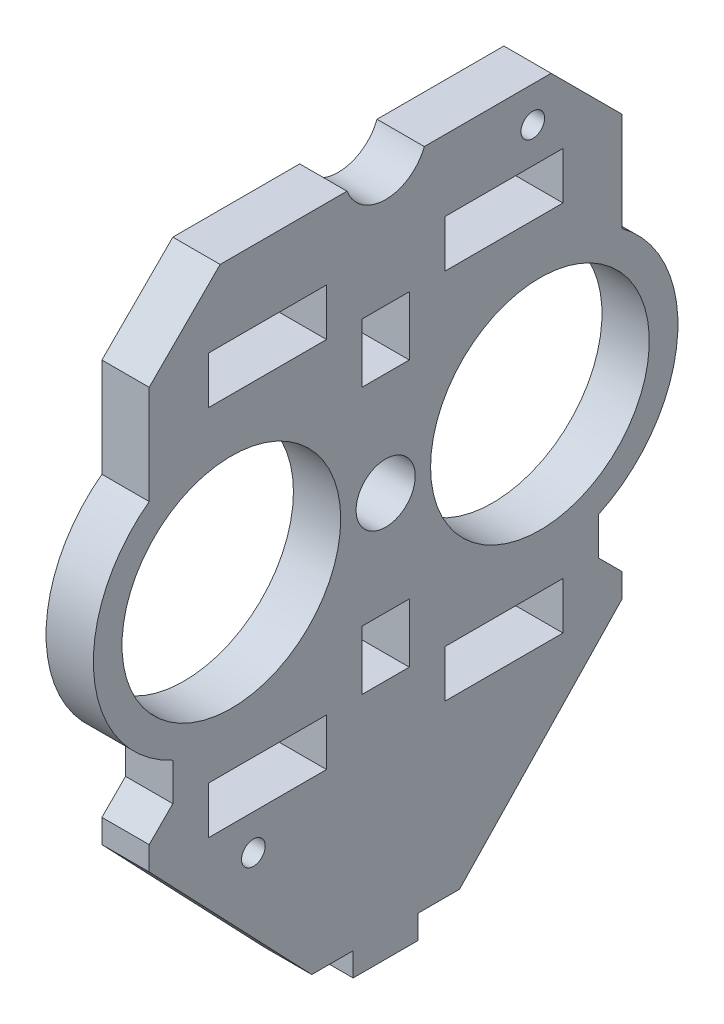
SolidWorks part; units mm, degrees
ref_plane "Front Plane" through (0, 0, 0) normal (0, 0, 1) x (1, 0, 0)
ref_plane "Top Plane" through (0, 0, 0) normal (0, 1, 0) x (1, 0, 0)
ref_plane "Right Plane" through (0, 0, 0) normal (1, 0, 0) x (0, 0, -1)
sketch "Sketch1" plane through (0, 0, 0) normal (1, 0, 0) x (0, 0, -1)
  line L0 (0, 86.3618) -> (0, -95.6447) construction
  line L1 (-34.45, 0) -> (67.35, 0) construction
  line L2 (-12.5, -64.29) -> (-40, -35.5)
  line L3 (-40, -31.5) -> (-40, -35.5)
  line L4 (-40, -31.5) -> (-36, -27.5)
  line L5 (-12.5, -64.29) -> (-12.5, -68.29)
  line L6 (-12.5, -68.29) -> (12.5, -68.29)
  line L7 (12.5, -64.29) -> (12.5, -68.29)
  line L8 (-36, -27.5) -> (-36, -21.1431)
  line L9 (-40, 35.5) -> (-40, 18.7571)
  line L10 (-40, 35.5) -> (-28, 47.5)
  line L11 (40, 35.5) -> (-40, 35.5) construction
  line L12 (40, 35.5) -> (40, 18.7571)
  line L13 (40, -35.5) -> (40, -31.5)
  line L14 (40, -31.5) -> (36, -27.5)
  line L15 (36, -27.5) -> (36, -21.1431)
  line L16 (12.5, -64.29) -> (40, -35.5)
  line L17 (40, -35.5) -> (30, -35.5) construction
  line L18 (40, 35.5) -> (28, 47.5)
  line L19 (-28, 47.5) -> (28, 47.5) construction
  line L20 (-28, 47.5) -> (-6.5383, 47.5)
  line L21 (6.5383, 47.5) -> (28, 47.5)
  line L22 (-40, -35.5) -> (-40, -27.5) construction
  line L24 (-30, -27.5) -> (-40, -27.5) construction
  circle A0 centre (0, 0) radius 76.29 construction
  circle A1 centre (-22.3739, -41.5) radius 2
  circle A2 centre (24.8916, 41.5) radius 2
  circle A3 centre (-26.1, 0) radius 23.3461 construction
  circle A4 centre (-26.1, 0) radius 18.5
  circle A5 centre (26.1, 0) radius 18.5
  circle A6 centre (26.1, 0) radius 23.3461 construction
  circle A7 centre (0, 0) radius 5
  circle A8 centre (0, 50) radius 7 construction
  arc A9 (-40, 18.7571) -> (-36, -21.1431) centre (-26.1, 0) ccw
  arc A10 (40, 18.7571) -> (36, -21.1431) centre (26.1, 0) cw
  circle A11 centre (-26.1, 0) radius 8.35 construction
  arc A12 (-6.5383, 47.5) -> (6.5383, 47.5) centre (0, 50) ccw
  circle A13 centre (70, 0) radius 2.65 construction
  circle A14 centre (-43.3013, -25) radius 7 construction
  point P14 (0, 0)
  point P16 (0, -76.29)
  point P20 (-62.4774, 0)
  point P27 (0, -68.29)
  point P30 (0, 56.7762)
  point P31 (0, 56.7762)
  dimension "D1" = 152.58
  dimension "D2" = 4
  dimension "D5" = 37
  dimension "D9" = 8
  dimension "D7" = 6
  dimension "D10" = 4
  dimension "D3" = 6
  dimension "D4" = 4
  dimension "D13" = 10
  dimension "D6" = 124.9548
  dimension "D8" = 25
  dimension "D11" = 12
  dimension "D12" = 12
  dimension "D15" = 4
extrude "Boss-Extrude1" add sketch "Sketch1" along normal blind 8
sketch "Sketch2" plane through (0, 0, 0) normal (-1, 0, 0) x (0, 0, 1)
  line L0 (0, -90.2636) -> (0, 91.611) construction
  line L1 (-93.4475, 0) -> (84.8595, 0) construction
  line L2 (10, -27.5) -> (10, -35.5)
  line L3 (-30, -27.5) -> (-10, -27.5)
  line L4 (-30, -27.5) -> (-30, -35.5)
  line L5 (-30, -35.5) -> (-10, -35.5)
  line L6 (-10, -27.5) -> (-10, -35.5)
  line L7 (30, -35.5) -> (10, -35.5)
  line L8 (30, -27.5) -> (30, -35.5)
  line L9 (30, -27.5) -> (10, -27.5)
  line L10 (30, 27.5) -> (10, 27.5)
  line L11 (30, 27.5) -> (30, 35.5)
  line L12 (30, 35.5) -> (10, 35.5)
  line L13 (-10, 27.5) -> (-10, 35.5)
  line L14 (-30, 35.5) -> (-10, 35.5)
  line L15 (-30, 27.5) -> (-30, 35.5)
  line L16 (-30, 27.5) -> (-10, 27.5)
  line L17 (10, 27.5) -> (10, 35.5)
  line L18 (4, 17.5) -> (4, 27.5)
  line L19 (-4, -17.5) -> (4, -17.5)
  line L20 (-4, -17.5) -> (-4, -27.5)
  line L21 (-4, -27.5) -> (4, -27.5)
  line L22 (4, -17.5) -> (4, -27.5)
  line L23 (-4, 27.5) -> (4, 27.5)
  line L24 (-4, 17.5) -> (-4, 27.5)
  line L25 (-4, 17.5) -> (4, 17.5)
  line L26 (5.5, -68.29) -> (5.5, -64.29)
  line L27 (-12.5, -68.29) -> (-5.5, -68.29)
  line L28 (-12.5, -68.29) -> (-12.5, -64.29)
  line L29 (-12.5, -64.29) -> (-5.5, -64.29)
  line L30 (-5.5, -68.29) -> (-5.5, -64.29)
  line L31 (12.5, -64.29) -> (5.5, -64.29)
  line L32 (12.5, -68.29) -> (12.5, -64.29)
  line L33 (12.5, -68.29) -> (5.5, -68.29)
  point P26 (0, -17.5)
  dimension "D1" = 27.5
  dimension "D2" = 20
  dimension "D3" = 20
  dimension "D4" = 8
  dimension "D5" = 8
  dimension "D6" = 10
  dimension "D7" = 4
  dimension "D8" = 7
extrude "Cut-Extrude1" cut sketch "Sketch2" against normal up to next
